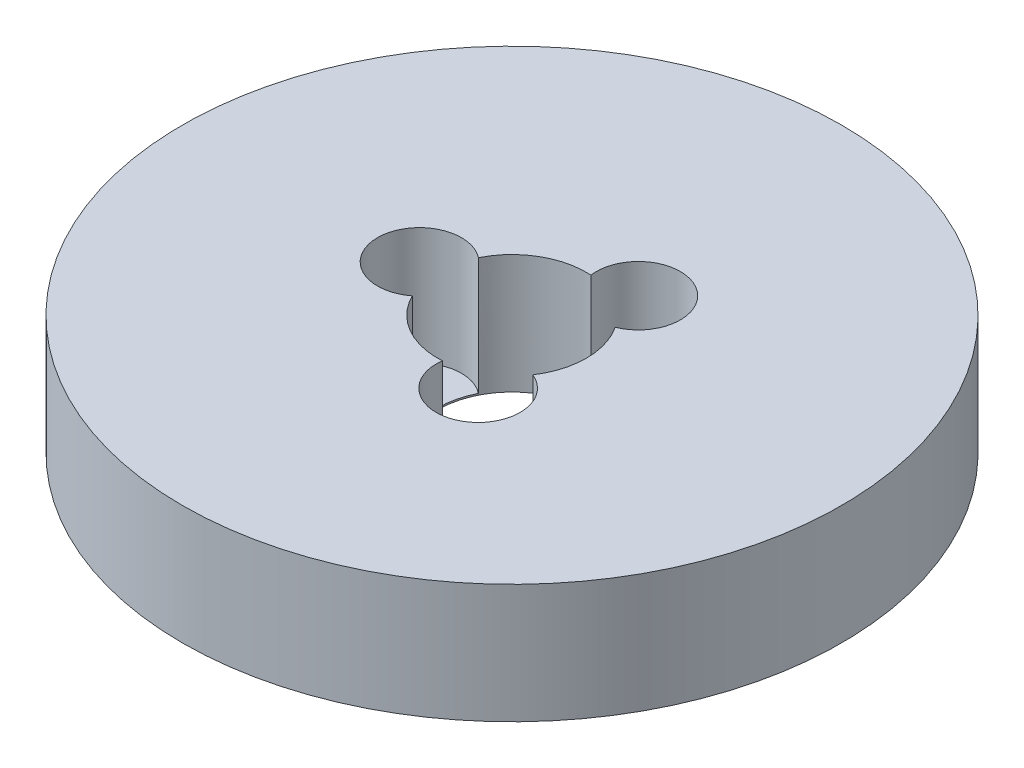
SolidWorks part; units mm, degrees
ref_plane "Front Plane" through (0, 0, 0) normal (0, 0, 1) x (1, 0, 0)
ref_plane "Top Plane" through (0, 0, 0) normal (0, 1, 0) x (1, 0, 0)
ref_plane "Right Plane" through (0, 0, 0) normal (1, 0, 0) x (0, 0, -1)
sketch "Sketch1" plane through (0, 0, 0) normal (0, 1, 0) x (1, 0, 0)
  circle A0 centre (0, 0) radius 77.5
  dimension "FLANGE_OD" = 155
extrude "Boss-Extrude1" add sketch "Sketch1" along normal blind 28
sketch "Sketch2" plane through (0, 0, 0) normal (0, 1, 0) x (1, 0, 0)
  circle A0 centre (0, 0) radius 17.5
  dimension "BORE_D" = 35
extrude "Cut-Extrude1" cut sketch "Sketch2" along normal through all
sketch "Sketch3" plane through (0, 28, 0) normal (0, 1, 0) x (1, 0, 0)
  circle A0 centre (0, 0) radius 21.7539 construction
  circle A1 centre (-21.7539, 0) radius 9.8712
  dimension "BOLT_D" = 19.7425
  dimension "BOLT_PCD" = 43.5077
extrude "Cut-Extrude2" cut sketch "Sketch3" against normal blind 27.6262
pattern_circular "CirPattern1" count 3 over 360 about axis through (0, 0, 0) along (0, 1, 0) of "Cut-Extrude2"
